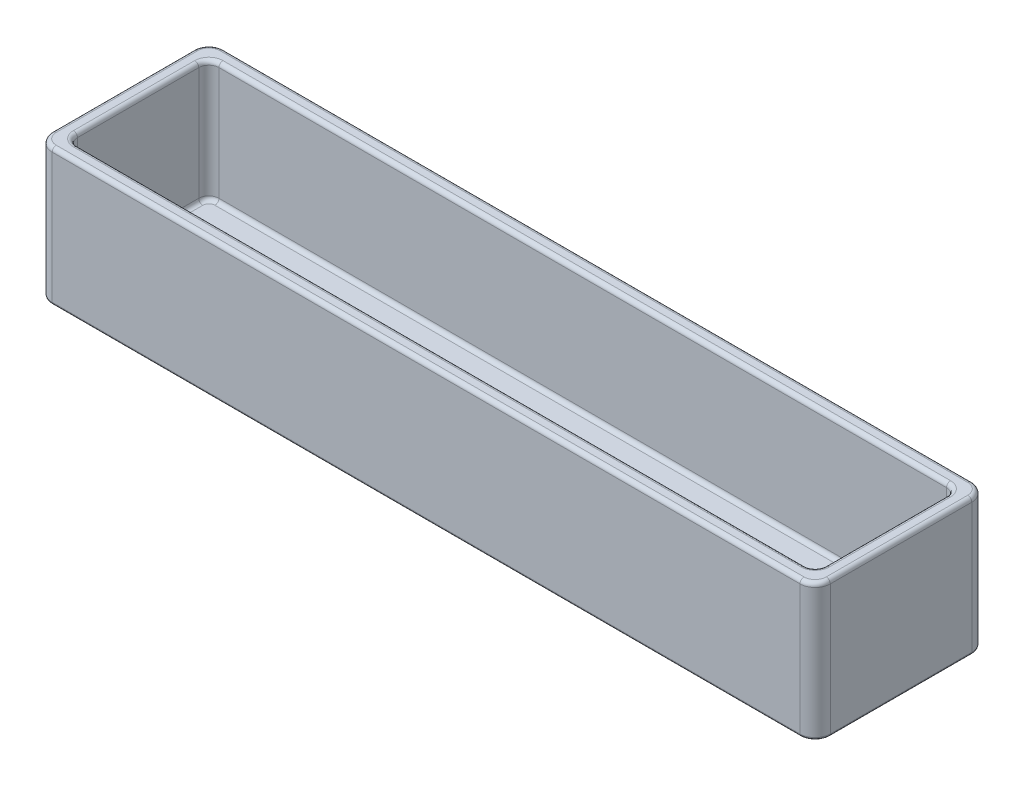
SolidWorks part; units mm, degrees
material "NEOPRENE"
ref_plane "Front" through (0, 0, 0) normal (0, 0, 1) x (1, 0, 0)
ref_plane "Top" through (0, 0, 0) normal (0, 1, 0) x (1, 0, 0)
ref_plane "Right" through (0, 0, 0) normal (1, 0, 0) x (0, 0, -1)
sketch "Sketch1" plane through (0, 0, 0) normal (0, 1, 0) x (1, 0, 0)
  line L0 (-117.475, 0) -> (-122.2375, 0) construction
  line L1 (-122.2375, 26.9875) -> (122.2375, 26.9875)
  line L2 (-122.2375, 26.9875) -> (-122.2375, -26.9875)
  line L3 (-122.2375, -26.9875) -> (122.2375, -26.9875)
  line L4 (122.2375, 26.9875) -> (122.2375, -26.9875)
  line L5 (-122.2375, 26.9875) -> (122.2375, -26.9875) construction
  line L6 (-122.2375, -26.9875) -> (122.2375, 26.9875) construction
  line L7 (117.475, 22.225) -> (-117.475, 22.225)
  line L8 (117.475, 22.225) -> (117.475, -22.225)
  line L9 (117.475, -22.225) -> (-117.475, -22.225)
  line L10 (-117.475, 22.225) -> (-117.475, -22.225)
  line L11 (117.475, 22.225) -> (-117.475, -22.225) construction
  line L12 (117.475, -22.225) -> (-117.475, 22.225) construction
  line L13 (0, 22.225) -> (0, 26.9875) construction
  point P0 (0, 0)
  point P6 (0, 0)
  dimension "D1" = 234.95
  dimension "D2" = 44.45
  dimension "THICKNESS" = 4.7625
extrude "Boss-Extrude1" add sketch "Sketch1" along normal blind 38.1
sketch "Sketch2" plane through (0, 0, 0) normal (0, -1, 0) x (1, 0, 0)
  line L4 (122.2375, -26.9875) -> (122.2375, 26.9875)
  line L5 (122.2375, 26.9875) -> (-122.2375, 26.9875)
  line L6 (-122.2375, 26.9875) -> (-122.2375, -26.9875)
  line L7 (-122.2375, -26.9875) -> (122.2375, -26.9875)
  line L8 (122.2375, -26.9875) -> (122.2375, 26.9875)
  line L9 (122.2375, 26.9875) -> (-122.2375, 26.9875)
  line L10 (-122.2375, 26.9875) -> (-122.2375, -26.9875)
  line L11 (-122.2375, -26.9875) -> (122.2375, -26.9875)
  arc A0 (105.9875, 2.6625) -> (105.9875, 6.8625) centre (105.9875, 4.7625) ccw construction
  arc A1 (105.9875, 6.8625) -> (105.9875, 2.6625) centre (105.9875, 4.7625) ccw construction
  arc A2 (74.9875, 2.6625) -> (74.9875, 6.8625) centre (74.9875, 4.7625) ccw construction
  arc A3 (74.9875, 6.8625) -> (74.9875, 2.6625) centre (74.9875, 4.7625) ccw construction
  arc A4 (105.9875, 2.6625) -> (105.9875, 6.8625) centre (105.9875, 4.7625) ccw
  arc A5 (105.9875, 6.8625) -> (105.9875, 2.6625) centre (105.9875, 4.7625) ccw
  arc A6 (74.9875, 2.6625) -> (74.9875, 6.8625) centre (74.9875, 4.7625) ccw
  arc A7 (74.9875, 6.8625) -> (74.9875, 2.6625) centre (74.9875, 4.7625) ccw
  dimension "D1" = 0
extrude "Boss-Extrude2" add sketch "Sketch2" along normal blind 4.7625
fillet "Fillet1" radius 3.175 4 edges at (117.475, 19.05, -22.225) (117.475, 19.05, 22.225) (-117.475, 19.05, 22.225) (-117.475, 19.05, -22.225)
fillet "Fillet2" radius 4.7625 4 edges at (-122.2375, 16.6687, -26.9875) (122.2375, 16.6687, -26.9875) (122.2375, 16.6687, 26.9875) (-122.2375, 16.6687, 26.9875)
sketch "Sketch4" plane through (0, -4.7625, 0) normal (0, -1, 0) x (1, 0, 0)
  line L2 (122.2375, -22.225) -> (122.2375, 22.225) construction
  line L3 (117.475, 26.9875) -> (-117.475, 26.9875) construction
  circle A0 centre (90.4875, 4.7625) radius 12.065
  dimension "D1" = 24.13
  dimension "D3" = 22.225
  dimension "D2" = 31.75
extrude "Cut-Extrude2" cut sketch "Sketch4" against normal through all
sketch "Sketch5" plane through (0, 0, -22.225) normal (0, 0, 1) x (1, 0, 0)
  line L0 (0, 0) -> (0, 19.05) construction
  line L1 (114.3, 38.1) -> (-114.3, 38.1) construction
  line L2 (-92.075, 0) -> (92.075, 0)
  line L3 (-92.075, 0) -> (-92.075, 38.1)
  line L4 (-92.075, 38.1) -> (92.075, 38.1)
  line L5 (92.075, 0) -> (92.075, 38.1)
  line L6 (-92.075, 0) -> (92.075, 38.1) construction
  line L7 (-92.075, 38.1) -> (92.075, 0) construction
  line L8 (114.3, 0) -> (-114.3, 0) construction
  dimension "D1" = 184.15
extrude "Boss-Extrude3" [suppressed] add sketch "Sketch5" along normal blind 1.651
fillet "Fillet3" [suppressed] radius 0.381
fillet "Fillet4" radius 1.27 8 edges at (116.5451, 0, -21.2951) (117.475, 0, 0) (116.5451, 0, 21.2951) (0, 0, 22.225) (-116.5451, 0, 21.2951) (-117.475, 0, 0) (-116.5451, 0, -21.2951) (0, 0, -22.225)
fillet "Fillet5" radius 0.762 8 edges at (-120.8426, -4.7625, 25.5926) (0, -4.7625, 26.9875) (120.8426, -4.7625, 25.5926) (122.2375, -4.7625, 0) (120.8426, -4.7625, -25.5926) (0, -4.7625, -26.9875) (-120.8426, -4.7625, -25.5926) (-122.2375, -4.7625, 0)
sketch "Sketch6" [suppressed] plane through (0, -4.7625, 0) normal (0, -1, 0) x (1, 0, 0)
  circle A0 centre (76.575, 6.35) radius 2.1 construction
  circle A1 centre (76.575, 6.35) radius 2.1
  circle A2 centre (107.575, 6.35) radius 2.1 construction
  circle A3 centre (107.575, 6.35) radius 2.1
extrude "Boss-Extrude4" [suppressed] add sketch "Sketch6" against normal up to surface (4.7625 mm away) up to face at (0, 0, 0)
sketch "Sketch7" [suppressed] plane through (0, -4.7625, 0) normal (0, -1, 0) x (1, 0, 0)
  circle A0 centre (-45.2, 0.936) radius 4.445
  circle A1 centre (45, 0.936) radius 4.445
  dimension "D1" = 8.89
extrude "Cut-Extrude3" [suppressed] cut sketch "Sketch7" against normal through all
sketch "Sketch8" [suppressed] plane through (0, 38.1, 0) normal (0, 1, 0) x (1, 0, 0)
  line L25 (-156.7727, 50.8) -> (156.7727, 50.8)
  line L26 (-156.7727, 50.8) -> (-156.7727, -50.8)
  line L27 (-156.7727, -50.8) -> (156.7727, -50.8)
  line L28 (156.7727, 50.8) -> (156.7727, -50.8)
  line L29 (-156.7727, 50.8) -> (156.7727, -50.8) construction
  line L30 (-156.7727, -50.8) -> (156.7727, 50.8) construction
  point P15 (0, 0)
  dimension "D2" = 101.6
  dimension "D1" = 313.5454
extrude "Cut-Extrude4" [suppressed] cut sketch "Sketch8" against normal blind 9.525
sketch "Sketch9" [suppressed] plane through (0, 0, 0) normal (0, 1, 0) x (1, 0, 0)
  line L1 (141.011, 38.276) -> (-141.011, 38.276)
  line L2 (141.011, 38.276) -> (141.011, -38.276)
  line L3 (141.011, -38.276) -> (-141.011, -38.276)
  line L4 (-141.011, 38.276) -> (-141.011, -38.276)
  line L5 (141.011, 38.276) -> (-141.011, -38.276) construction
  line L6 (141.011, -38.276) -> (-141.011, 38.276) construction
  point P0 (0, 0)
  dimension "D1" = 76.552
  dimension "D2" = 282.022
extrude "Cut-Extrude5" [suppressed] cut sketch "Sketch9" along normal offset from surface 2.54 and the other way through all up to face at (0, 38.1, 0)
sketch "Sketch10" [suppressed] plane through (0, 0, 0) normal (0, 1, 0) x (1, 0, 0)
  line L1 (-134.0132, -36.4455) -> (134.0132, -36.4455)
  line L2 (-134.0132, -36.4455) -> (-134.0132, 36.4455)
  line L3 (-134.0132, 36.4455) -> (134.0132, 36.4455)
  line L4 (134.0132, -36.4455) -> (134.0132, 36.4455)
  line L5 (-134.0132, -36.4455) -> (134.0132, 36.4455) construction
  line L6 (-134.0132, 36.4455) -> (134.0132, -36.4455) construction
  point P0 (0, 0)
  dimension "D1" = 268.0264
  dimension "D2" = 72.8909
extrude "Cut-Extrude6" [suppressed] cut sketch "Sketch10" along normal through all
sketch "Sketch11" [suppressed] plane through (0, -2.3368, 0) normal (0, -1, 0) x (1, 0, 0)
  line L1 (-127.2014, -33.7924) -> (127.2014, -33.7924)
  line L2 (-127.2014, -33.7924) -> (-127.2014, 33.7924)
  line L3 (-127.2014, 33.7924) -> (127.2014, 33.7924)
  line L4 (127.2014, -33.7924) -> (127.2014, 33.7924)
  line L5 (-127.2014, -33.7924) -> (127.2014, 33.7924) construction
  line L6 (-127.2014, 33.7924) -> (127.2014, -33.7924) construction
  point P0 (0, 0)
  dimension "D1" = 254.4028
  dimension "D2" = 67.5847
extrude "Cut-Extrude7" [suppressed] cut sketch "Sketch11" against normal offset from surface (37.8968 mm away) 2.54 up to face at (0, 38.1, 0)
sketch "Sketch12" [suppressed] plane through (0, 0, 0) normal (0, 1, 0) x (1, 0, 0)
  line L1 (-131.4623, -33.804) -> (131.4623, -33.804)
  line L2 (-131.4623, -33.804) -> (-131.4623, 33.804)
  line L3 (-131.4623, 33.804) -> (131.4623, 33.804)
  line L4 (131.4623, -33.804) -> (131.4623, 33.804)
  line L5 (-131.4623, -33.804) -> (131.4623, 33.804) construction
  line L6 (-131.4623, 33.804) -> (131.4623, -33.804) construction
  point P0 (0, 0)
  dimension "D1" = 262.9246
  dimension "D2" = 67.6081
extrude "Cut-Extrude8" [suppressed] cut sketch "Sketch12" along normal through all
sketch "Sketch13" [suppressed] plane through (0, 0, 22.225) normal (0, 0, -1) x (-1, 0, 0)
  line L0 (64.6891, 28.575) -> (64.6891, -4.7625)
  line L1 (114.3, 28.575) -> (-114.3, 28.575) construction
  line L2 (-117.475, -4.7625) -> (117.475, -4.7625) construction
  dimension "D1" = 33.3375
fillet "Fillet6" radius 1.27 16 edges at (116.5451, 38.1, -21.2951) (117.475, 38.1, 0) (116.5451, 38.1, 21.2951) (0, 38.1, 22.225) (-116.5451, 38.1, 21.2951) (-117.475, 38.1, 0) (-116.5451, 38.1, -21.2951) (120.8426, 38.1, -25.5926) (122.2375, 38.1, 0) (120.8426, 38.1, 25.5926) (0, 38.1, 26.9875) (-120.8426, 38.1, 25.5926) (-122.2375, 38.1, 0) (-120.8426, 38.1, -25.5926) (0, 38.1, -22.225) (0, 38.1, -26.9875)
fillet "Fillet7" [suppressed] radius 1.27
fillet "Fillet8" [suppressed] radius 1.27
fillet "Fillet9" radius 0.508 3 edges at (105.9875, 0, 2.6625) (74.9875, 0, 2.6625) (90.4875, 0, -7.3025)
sketch "Sketch14" plane through (0, 0, -26.9875) normal (0, 0, -1) x (-1, 0, 0)
  line L0 (0, -4.7625) -> (0, 38.1) construction
  line L1 (117.475, -4.7625) -> (-117.475, -4.7625) construction
  line L2 (-117.475, 38.1) -> (117.475, 38.1) construction
  line L3 (55.5625, 38.1) -> (-55.5625, -4.7625)
  line L4 (122.2375, 36.83) -> (122.2375, -4.0005) construction
  line L5 (55.5625, 38.1) -> (122.2375, 38.1)
  line L6 (122.2375, 38.1) -> (122.2375, -4.7625)
  line L7 (122.2375, -4.7625) -> (-55.5625, -4.7625)
  point P8 (0, 16.6687)
  dimension "D1" = 177.8
sketch "Sketch15" plane through (0, 0, -26.9875) normal (0, 0, -1) x (-1, 0, 0)
  line L4 (55.5625, 38.1) -> (-55.5625, -4.7625)
  line L5 (-55.5625, -4.7625) -> (122.2375, -4.7625)
  line L6 (122.2375, -4.7625) -> (122.2375, 38.1)
  line L7 (122.2375, 38.1) -> (55.5625, 38.1)
  line L8 (55.5625, 38.1) -> (-55.5625, -4.7625)
  line L9 (-55.5625, -4.7625) -> (122.2375, -4.7625)
  line L10 (122.2375, -4.7625) -> (122.2375, 38.1)
  line L11 (122.2375, 38.1) -> (55.5625, 38.1)
  dimension "D1" = 0
extrude "Cut-Extrude9" [suppressed] cut sketch "Sketch15" against normal through all
sketch "Sketch16" [suppressed] plane through (0, 0, -26.9875) normal (0, 0, -1) x (-1, 0, 0)
  line L0 (55.5625, 38.1) -> (-122.2375, 38.1)
  line L1 (-122.2375, 38.1) -> (-122.2375, -4.7625)
  line L2 (-122.2375, -4.7625) -> (-55.5625, -4.7625)
  line L3 (-122.2375, -4.0005) -> (-122.2375, 36.83) construction
  line L4 (55.5625, 38.1) -> (-55.5625, -4.7625)
  line L5 (-55.5625, -4.7625) -> (122.2375, -4.7625)
  line L6 (122.2375, -4.7625) -> (122.2375, 38.1)
  line L7 (122.2375, 38.1) -> (55.5625, 38.1)
  line L8 (55.5625, 38.1) -> (-55.5625, -4.7625)
  dimension "D1" = 0
extrude "Cut-Extrude10" [suppressed] cut sketch "Sketch16" against normal through all
sketch "Sketch17" [suppressed] plane through (0, 0, -26.9875) normal (0, 0, -1) x (-1, 0, 0)
  line L0 (0, 28.575) -> (0, -4.7625) construction
  line L1 (-117.475, 28.575) -> (117.475, 28.575) construction
  line L2 (117.475, -4.7625) -> (-117.475, -4.7625) construction
  line L3 (-55.5625, -4.7625) -> (55.5625, 28.575)
  line L4 (-122.2375, -4.0005) -> (-122.2375, 27.305) construction
  line L5 (55.5625, 28.575) -> (122.2375, 28.575)
  line L6 (122.2375, 28.575) -> (122.2375, -4.7625)
  line L7 (122.2375, -4.7625) -> (-55.5625, -4.7625)
  line L8 (122.2375, 27.305) -> (122.2375, -4.0005) construction
  point P8 (0, 11.9063)
  dimension "D1" = 177.8
sketch "Sketch18" [suppressed] plane through (0, 0, -26.9875) normal (0, 0, -1) x (-1, 0, 0)
  line L4 (55.5625, 28.575) -> (-55.5625, -4.7625)
  line L5 (122.2375, 28.575) -> (55.5625, 28.575)
  line L6 (122.2375, -4.7625) -> (122.2375, 28.575)
  line L7 (-55.5625, -4.7625) -> (122.2375, -4.7625)
  line L8 (55.5625, 28.575) -> (-55.5625, -4.7625)
  line L9 (122.2375, 28.575) -> (55.5625, 28.575)
  line L10 (122.2375, -4.7625) -> (122.2375, 28.575)
  line L11 (-55.5625, -4.7625) -> (122.2375, -4.7625)
  dimension "D1" = 0
extrude "Cut-Extrude11" [suppressed] cut sketch "Sketch18" against normal through all
sketch "Sketch19" [suppressed] plane through (0, 0, -26.9875) normal (0, 0, -1) x (-1, 0, 0)
  line L0 (-55.5625, -4.7625) -> (-122.2375, -4.7625)
  line L2 (-122.2375, -4.7625) -> (-122.2375, 28.575)
  line L3 (-122.2375, 28.575) -> (55.5625, 28.575)
  line L4 (55.5625, 28.575) -> (-55.5625, -4.7625)
  line L5 (122.2375, 28.575) -> (55.5625, 28.575)
  line L6 (122.2375, -4.7625) -> (122.2375, 28.575)
  line L7 (-55.5625, -4.7625) -> (122.2375, -4.7625)
  line L8 (55.5625, 28.575) -> (-55.5625, -4.7625)
  line L12 (-122.2375, -4.0005) -> (-122.2375, 27.305) construction
  dimension "D1" = 0
extrude "Cut-Extrude12" [suppressed] cut sketch "Sketch19" against normal through all and the other way blind 2.54
equation "\"D1@Boss-Extrude2\"=\"THICKNESS\""
